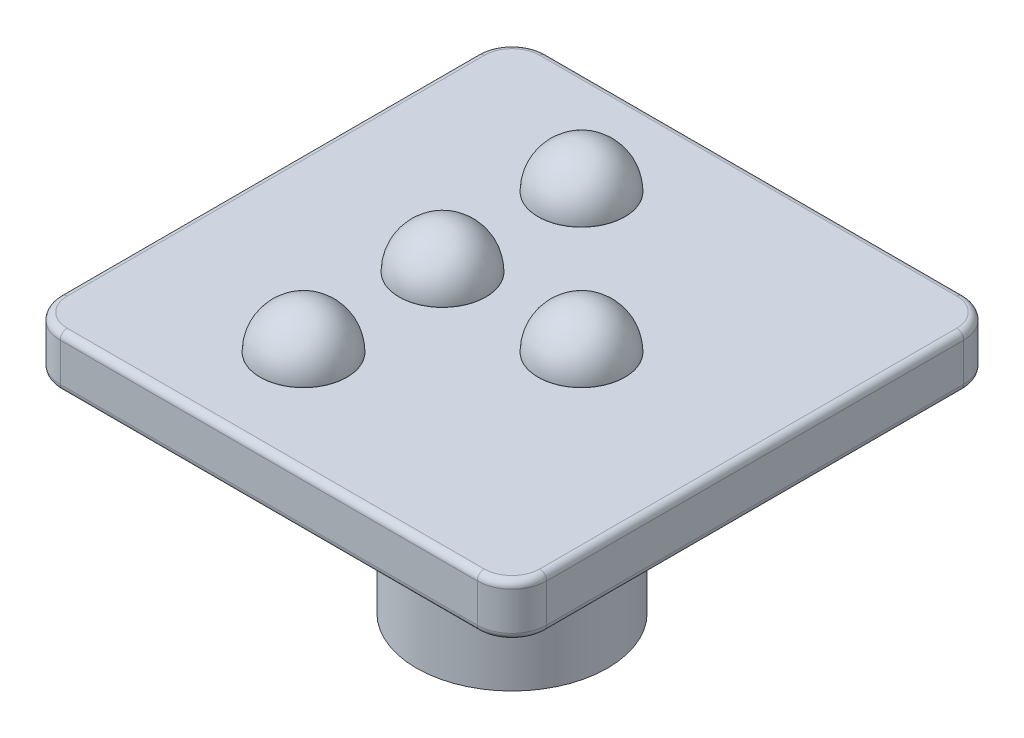
SolidWorks part; units mm, degrees
ref_plane "Front Plane" through (0, 0, 0) normal (0, 0, 1) x (1, 0, 0)
ref_plane "Top Plane" through (0, 0, 0) normal (0, 1, 0) x (1, 0, 0)
ref_plane "Right Plane" through (0, 0, 0) normal (1, 0, 0) x (0, 0, -1)
sketch "Sketch1" plane through (0, 0, 0) normal (0, 1, 0) x (1, 0, 0)
  line L1 (-7.3247, 4.3967) -> (4.6753, 4.3967)
  line L2 (-8.3247, 3.3967) -> (-8.3247, -8.6033)
  line L3 (-7.3247, -9.6033) -> (4.6753, -9.6033)
  line L4 (5.6753, 3.3967) -> (5.6753, -8.6033)
  arc A0 (-8.3247, -8.6033) -> (-7.3247, -9.6033) centre (-7.3247, -8.6033) ccw
  arc A1 (4.6753, -9.6033) -> (5.6753, -8.6033) centre (4.6753, -8.6033) ccw
  arc A2 (4.6753, 4.3967) -> (5.6753, 3.3967) centre (4.6753, 3.3967) cw
  arc A3 (-7.3247, 4.3967) -> (-8.3247, 3.3967) centre (-7.3247, 3.3967) ccw
  point P8 (5.6753, -9.6033)
  point P11 (5.6753, 4.3967)
  point P14 (-8.3247, 4.3967)
  dimension "D3" = 1
  dimension "D1" = 14
  dimension "D2" = 14
extrude "Boss-Extrude1" add sketch "Sketch1" along normal blind 1.5
sketch "Sketch2" plane through (0, 0, 0) normal (0, -1, 0) x (1, 0, 0)
  line L0 (-7.3247, 9.6033) -> (4.6753, 9.6033) construction
  line L1 (5.6753, 8.6033) -> (5.6753, -3.3967) construction
  line L2 (-1.3247, -4.3967) -> (-1.3247, 9.6033) construction
  line L3 (-8.3247, 2.6033) -> (5.6753, 2.6033) construction
  line L4 (-8.3247, -3.3967) -> (-8.3247, 8.6033) construction
  circle A0 centre (-1.3247, 2.6033) radius 2.75
  dimension "D1" = 7
  dimension "D2" = 7
extrude "Boss-Extrude2" add sketch "Sketch2" along normal blind 6
sketch "Sketch3" plane through (0, -6, 0) normal (0, -1, 0) x (1, 0, 0)
  line L0 (-1.3247, 5.3533) -> (-1.3247, -0.1467) construction
  line L1 (-3.3247, 3.1533) -> (0.6753, 3.1533)
  line L2 (-3.3247, 3.1533) -> (-3.3247, 2.0533)
  line L3 (-3.3247, 2.0533) -> (0.6753, 2.0533)
  line L4 (0.6753, 3.1533) -> (0.6753, 2.0533)
  line L5 (-1.8747, 4.6033) -> (-0.7747, 4.6033)
  line L6 (-1.8747, 4.6033) -> (-1.8747, 0.6033)
  line L7 (-1.8747, 0.6033) -> (-0.7747, 0.6033)
  line L8 (-0.7747, 4.6033) -> (-0.7747, 0.6033)
  line L9 (-4.0747, 2.6033) -> (1.4253, 2.6033) construction
  circle A3 centre (-1.3247, 2.6033) radius 2.75 construction
  circle A4 centre (-1.3247, 2.6033) radius 2.75 construction
  dimension "D7" = 0.55
  dimension "D1" = 4
  dimension "D2" = 1.1
  dimension "D3" = 1.1
  dimension "D4" = 4
  dimension "D8" = 0.55
extrude "Cut-Extrude1" cut sketch "Sketch3" against normal blind 6 contours L8 L5 L6 L1 | L1 L8 L3 L4 | L8 L1 L6 L3 | L6 L1 L2 L3 | L8 L3 L6 L7 region at (-2.5997, -6, 2.6033) region at (-1.3247, -6, 3.8783) region at (-1.3247, -6, 2.6033) region at (-0.0497, -6, 2.6033) region at (-1.3247, -6, 1.3283)
chamfer "Chamfer1" distance 0.3 angle 45 12 edges at (-1.3247, -6, 0.6033) (-1.8747, -6, 1.3283) (-2.5997, -6, 2.0533) (-3.3247, -6, 2.6033) (-2.5997, -6, 3.1533) (-0.7747, -6, 1.3283) (-0.0497, -6, 2.0533) (0.6753, -6, 2.6033) (-0.0497, -6, 3.1533) (-0.7747, -6, 3.8783) (-1.3247, -6, 4.6033) (-1.8747, -6, 3.8783)
fillet "Fillet1" radius 1 1 edges at (-1.3247, 0, -0.1467)
sketch "Sketch4" plane through (0, 1.5, 0) normal (0, 1, 0) x (1, 0, 0)
  line L0 (-1.3247, 4.3967) -> (-1.3247, -9.6033) construction
  line L1 (4.6753, 4.3967) -> (-7.3247, 4.3967) construction
  line L2 (-7.3247, -9.6033) -> (4.6753, -9.6033) construction
  line L3 (5.6753, -2.6033) -> (-8.3247, -2.6033) construction
  line L4 (-8.3247, 3.3967) -> (-8.3247, -8.6033) construction
  line L5 (5.6753, -8.6033) -> (5.6753, 3.3967) construction
  line L6 (-3.3247, 4.3967) -> (-3.3247, -9.6033) construction
  line L7 (0.6753, 4.3967) -> (0.6753, -9.6033) construction
  line L8 (-8.3247, 1.3967) -> (5.6753, 1.3967) construction
  line L9 (5.6753, -6.6033) -> (-8.3247, -6.6033) construction
  circle A0 centre (-3.3247, 1.3967) radius 1.25
  circle A1 centre (0.6753, -2.6033) radius 1.25
  circle A2 centre (-3.3247, -2.6033) radius 1.25
  circle A3 centre (-3.3247, -6.6033) radius 1.25
  dimension "D1" = 4
  dimension "D2" = 4
  dimension "D3" = 2
  dimension "D4" = 2
extrude "Boss-Extrude3" add sketch "Sketch4" along normal blind 0.01
dome "Dome1" faces to dome 1 distance 1.25 reverse direction no elliptical dome no face at (-3.3247, 1.51, -0.1467) parameters "D1"=1.25
dome "Dome3" faces to dome 1 distance 1.25 reverse direction no elliptical dome no face at (-3.3247, 1.51, 3.8533) parameters "D1"=1.25
dome "Dome4" faces to dome 1 distance 1.25 reverse direction no elliptical dome no face at (0.6753, 1.51, 3.8533) parameters "D1"=1.25
dome "Dome5" faces to dome 1 distance 1.25 reverse direction no elliptical dome no face at (-3.3247, 1.51, 7.8533) parameters "D1"=1.25
fillet "Fillet3" radius 0.2 16 edges at (5.3824, 1.5, -4.1038) (5.6753, 1.5, 2.6033) (5.3824, 1.5, 9.3104) (-1.3247, 1.5, 9.6033) (-8.0318, 1.5, 9.3104) (-8.0318, 1.5, -4.1038) (-8.3247, 1.5, 2.6033) (-1.3247, 1.5, -4.3967) (5.3824, 0, 9.3104) (5.6753, 0, 2.6033) (5.3824, 0, -4.1038) (-1.3247, 0, -4.3967) (-8.0318, 0, -4.1038) (-8.3247, 0, 2.6033) (-8.0318, 0, 9.3104) (-1.3247, 0, 9.6033)
